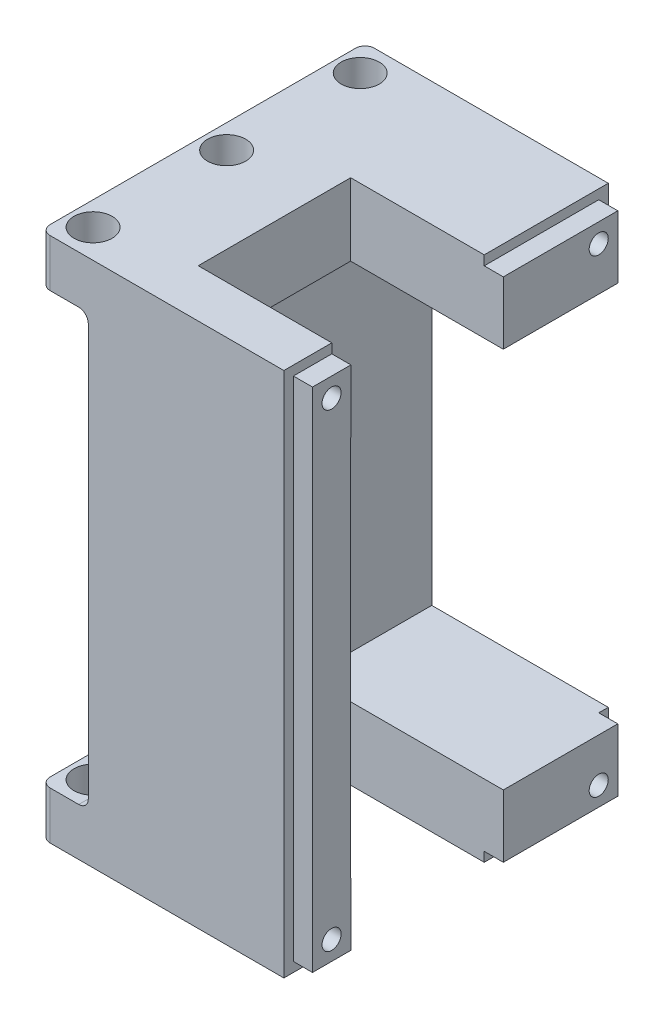
SolidWorks part; units mm, degrees
ref_plane "前视基准面" through (0, 0, 0) normal (0, 0, 1) x (1, 0, 0)
ref_plane "上视基准面" through (0, 0, 0) normal (0, 1, 0) x (1, 0, 0)
ref_plane "右视基准面" through (0, 0, 0) normal (1, 0, 0) x (0, 0, -1)
other "Configuration Table"
sketch "草图1" plane through (0, 0, 0) normal (0, 0, 1) x (1, 0, 0)
  line L0 (-1000, 0) -> (49000, 0) construction
  line L1 (-10.25, -20) -> (10.25, -20)
  line L2 (-10.25, -20) -> (-10.25, 20)
  line L3 (-10.25, 20) -> (10.25, 20)
  line L4 (10.25, -20) -> (10.25, 20)
  line L5 (-10.25, -20) -> (10.25, 20) construction
  line L6 (-10.25, 20) -> (10.25, -20) construction
  line L7 (-5, 15) -> (5, 15)
  line L8 (-5, 15) -> (-5, 25)
  line L9 (-5, 25) -> (5, 25)
  line L10 (5, 15) -> (5, 25)
  line L11 (-5, 15) -> (5, 25) construction
  line L12 (-5, 25) -> (5, 15) construction
  line L14 (-10.25, -35.1417) -> (10.25, -35.1417)
  line L15 (-10.25, -35.1417) -> (-10.25, 35.1417)
  line L16 (-10.25, 35.1417) -> (10.25, 35.1417)
  line L17 (10.25, -35.1417) -> (10.25, 35.1417)
  line L18 (-10.25, -35.1417) -> (10.25, 35.1417) construction
  line L19 (-10.25, 35.1417) -> (10.25, -35.1417) construction
  circle A0 centre (-5, 25) radius 2
  circle A1 centre (5, 25) radius 2
  circle A2 centre (5, -25) radius 2
  circle A3 centre (-5, -25) radius 2
  point P0 (0, 0)
  point P6 (0, 20)
  point P19 (0, 0)
  dimension "D5" = 4
  dimension "D6" = 4
  dimension "D1" = 20.5
  dimension "D2" = 40
  dimension "D3" = 10
  dimension "D4" = 10
extrude "凸台-拉伸1" add sketch "草图1" along normal blind 29 contours A1 L10 L3 L17 L16 L15 L8 A0 L9 | L14 L17 L1 L15 A2 A3 | A1 L9 A0 L8 L3 L10
sketch "草图2" plane through (0, 0, 29) normal (0, 0, 1) x (1, 0, 0)
  line L1 (-10.25, 35.1417) -> (10.25, 35.1417)
  line L2 (-10.25, 35.1417) -> (-10.25, -35.1417)
  line L3 (-10.25, -35.1417) -> (10.25, -35.1417)
  line L4 (10.25, 35.1417) -> (10.25, -35.1417)
extrude "凸台-拉伸2" add sketch "草图2" along normal blind 3
sketch "草图3" plane through (0, 0, 0) normal (0, 0, -1) x (-1, 0, 0)
  line L0 (-10.25, -35.1417) -> (-10.25, -20) construction
  line L1 (-10.25, -27.5709) -> (10.25, -27.5709)
  line L2 (-10.25, -27.5709) -> (-10.25, 27.5709)
  line L3 (-10.25, 27.5709) -> (10.25, 27.5709)
  line L4 (10.25, -27.5709) -> (10.25, 27.5709)
  line L5 (10.25, 20) -> (10.25, 35.1417) construction
  line L7 (-10.25, -35.1417) -> (10.25, -35.1417)
  line L8 (-10.25, -35.1417) -> (-10.25, 35.1417)
  line L9 (-10.25, 35.1417) -> (10.25, 35.1417)
  line L10 (10.25, -35.1417) -> (10.25, 35.1417)
  line M2 (-10.25, -35.1417) -> (10.25, -35.1417)
  line M3 (10.25, -35.1417) -> (10.25, -20)
  line M5 (-10.25, -20) -> (-10.25, -35.1417)
extrude "切除-拉伸1" cut sketch "草图3" against normal through all contours L1 M5 M2 M3 | L3 L10 L9 L8
sketch "草图5" plane through (0, -27.5709, 0) normal (0, -1, 0) x (1, 0, 0)
  line L0 (0, 0) -> (0, 2.5)
  circle A0 centre (0, 2.5) radius 2.5
  dimension "D2" = 5
  dimension "D1" = 2.5
extrude "凸台-拉伸3" add sketch "草图5" along normal blind 10
sketch "草图8" plane through (0, 27.5709, 0) normal (0, 1, 0) x (1, 0, 0)
  line L0 (0, 0) -> (0, -2.5)
  line L1 (0, -2.5) -> (0, -16.5)
  line L2 (0, -16.5) -> (0, -26.5)
  circle A0 centre (0, -16.5) radius 1.6
  circle A1 centre (0, -26.5) radius 1.6
  dimension "D4" = 3.2
  dimension "D5" = 3.2
  dimension "D1" = 2.5
  dimension "D2" = 14
  dimension "D3" = 10
extrude "切除-拉伸2" cut sketch "草图8" against normal up to next
sketch "草图9" plane through (0, -27.5709, 0) normal (0, -1, 0) x (1, 0, 0)
  line L1 (-10.25, 32) -> (10.25, 32)
  line L2 (-10.25, 32) -> (-10.25, 0)
  line L3 (-10.25, 0) -> (10.25, 0)
  line L4 (10.25, 32) -> (10.25, 0)
extrude "切除-拉伸3" cut sketch "草图9" along normal through all
sketch "草图12" plane through (0, 0, 0) normal (0, 0, -1) x (-1, 0, 0)
  line L1 (-10.25, 27.5709) -> (10.25, 27.5709)
  line L2 (-10.25, 27.5709) -> (-10.25, 20)
  line L3 (-10.25, 20) -> (10.25, 20)
  line L4 (10.25, 27.5709) -> (10.25, 20)
  circle A0 centre (-5, 25) radius 2
  circle A1 centre (5, 25) radius 2
extrude "凸台-拉伸5" add sketch "草图12" against normal blind 30
sketch "草图13" plane through (0, 27.5709, 0) normal (0, 1, 0) x (1, 0, 0)
  line L0 (0, 0) -> (0, -32)
  line L1 (10.25, -32) -> (-10.25, -32) construction
  line L2 (0, 0) -> (0, -10)
  line L3 (0, 0) -> (0, -2.5275)
  line L4 (0, 0) -> (0, -5)
  circle A2 centre (0, -5) radius 2.5
  circle A3 centre (0, -5) radius 4
  dimension "D3" = 5
  dimension "D4" = 5
  dimension "D5" = 8
  dimension "D1" = 32
  dimension "D2" = 10
extrude "凸台-拉伸6" add sketch "草图13" along normal blind 10 contours L4 A3 L2 A2 | L2 A3 L4 A2
sketch "草图15" plane through (0, 0, 0) normal (1, 0, 0) x (0, 0, -1)
  line L0 (-1, 27.5709) -> (0, 27.5709)
  line L1 (-1, 27.5709) -> (-1, 28.676)
  line L2 (-1, 27.5709) -> (-1, 37.5709) construction
  line L3 (-5, -962.4291) -> (-5, 49037.5709) construction
  line L4 (-2.5, 37.5709) -> (-7.5, 37.5709) construction
  arc A0 (-1, 28.676) -> (0, 27.5709) centre (0.1107, 28.676) ccw
  point P13 (-5, 37.5709)
revolve "旋转1" add sketch "草图15" angle 360 about L3
ref_plane "基准面1" through (0, 0, 5) normal (0, 0, 1) x (1, 0, 0)
sketch "草图16" plane through (0, 0, 5) normal (0, 0, 1) x (1, 0, 0)
  line L0 (0, 37.5709) -> (0, 33.5709)
  line L1 (2.5, 37.5709) -> (-2.5, 37.5709) construction
  circle A0 centre (0, 33.5709) radius 1.5
  dimension "D2" = 3
  dimension "D1" = 4
extrude "切除-拉伸5" cut sketch "草图16" against normal through all
sketch "草图17" plane through (0, 0, 0) normal (1, 0, 0) x (0, 0, -1)
  line L0 (-5, 37.5709) -> (-5, 33.5709)
  line L1 (-2.5, 37.5709) -> (-7.5, 37.5709) construction
  line L2 (-5, 11.275) -> (-5, -11.275) construction
  circle A0 centre (-5, 33.5709) radius 1.5
  dimension "D2" = 3
  dimension "D1" = 4
extrude "切除-拉伸6" cut sketch "草图17" against normal through all
sketch "草图19" plane through (0, -27.5709, 0) normal (0, -1, 0) x (1, 0, 0)
  line L0 (0, 0) -> (0, 5)
  line L1 (10.25, 0) -> (-10.25, 0) construction
  circle A0 centre (0, 5) radius 2.5
  circle A1 centre (0, 5) radius 4
  dimension "D2" = 5
  dimension "D3" = 8
  dimension "D1" = 5
extrude "凸台-拉伸7" add sketch "草图19" along normal blind 10
sketch "草图20" plane through (0, 0, 0) normal (1, 0, 0) x (0, 0, -1)
  line L0 (-1, -27.5709) -> (0, -27.5709)
  line L1 (-1, -27.5709) -> (-1, -28.5709)
  line L2 (-1, -37.5709) -> (-1, -27.5709) construction
  line L3 (-5, -1027.5709) -> (-5, 48972.4291) construction
  line L4 (-9, -27.5709) -> (-1, -27.5709) construction
  arc A0 (-1, -28.5709) -> (0, -27.5709) centre (0, -28.5709) cw
  point P13 (-5, -27.5709)
  dimension "D1" = 1
revolve "旋转2" add sketch "草图20" angle 360 about L3
sketch "草图21" plane through (0, 0, 5) normal (0, 0, 1) x (1, 0, 0)
  line L0 (0, -37.5709) -> (0, -33.5709)
  line L1 (-4, -37.5709) -> (4, -37.5709) construction
  circle A0 centre (0, -33.5709) radius 1.5
  dimension "D2" = 3
  dimension "D1" = 4
extrude "切除-拉伸7" cut sketch "草图21" against normal through all
sketch "草图22" plane through (0, 0, 0) normal (1, 0, 0) x (0, 0, -1)
  line L0 (-5, -37.5709) -> (-5, -33.5709)
  line L1 (-9, -37.5709) -> (-1, -37.5709) construction
  line L2 (-5, 11.275) -> (-5, -11.275) construction
  circle A0 centre (-5, -33.5709) radius 1.5
  dimension "D2" = 3
  dimension "D1" = 4
extrude "切除-拉伸8" cut sketch "草图22" against normal through all
sketch "草图23" plane through (0, 0, 32) normal (0, 0, 1) x (1, 0, 0)
  line L1 (-10.25, 27.5709) -> (10.25, 27.5709)
  line L2 (-10.25, 27.5709) -> (-10.25, -27.5709)
  line L3 (-10.25, -27.5709) -> (10.25, -27.5709)
  line L4 (10.25, 27.5709) -> (10.25, -27.5709)
extrude "凸台-拉伸8" add sketch "草图23" along normal blind 2
sketch "草图24" plane through (-10.25, 0, 0) normal (-1, 0, 0) x (0, 0, 1)
  line L0 (34, -27.5709) -> (0, -27.5709) construction
  line L1 (34, 27.5709) -> (24, 27.5709)
  line L2 (34, 27.5709) -> (34, -27.5709)
  line L3 (34, -27.5709) -> (24, -27.5709)
  line L4 (24, 27.5709) -> (24, -27.5709)
  dimension "D1" = 10
extrude "凸台-拉伸9" add sketch "草图24" along normal blind 2
sketch "草图25" plane through (10.25, 0, 0) normal (1, 0, 0) x (0, 0, -1)
  line L0 (-34, 27.5709) -> (-21, 27.5709)
  line L1 (-34, 27.5709) -> (0, 27.5709) construction
  line L2 (-21, 27.5709) -> (-17, 27.5709)
  line L3 (-17, 27.5709) -> (-17, -27.5709)
  line L6 (-17, -27.5709) -> (-25, -27.5709)
  line L7 (-34, -27.5709) -> (0, -27.5709) construction
  line L8 (-25, -27.5709) -> (-25, 27.5709)
  line M5 (-29, 20) -> (0, 20)
  line M7 (0, 27.5709) -> (-34, 27.5709)
  line M9 (-34, -27.5709) -> (0, -27.5709)
  line M11 (0, -20) -> (-29, -20)
  dimension "D1" = 13
  dimension "D2" = 4
  dimension "D3" = 8
extrude "切除-拉伸9" cut sketch "草图25" against normal blind 16 contours L8 L3 M9 M11 | L8 L3 M5 M7
sketch "草图26" plane through (0, 0, 29) normal (0, 0, -1) x (-1, 0, 0)
  circle A0 centre (-5, 25) radius 2
  circle A1 centre (5, 25) radius 2
  circle A2 centre (-5, -25) radius 2
  circle A3 centre (5, -25) radius 2
extrude "凸台-拉伸10" add sketch "草图26" along normal blind 20
sketch "草图27" plane through (0, -27.5709, 0) normal (0, -1, 0) x (1, 0, 0)
  line L1 (-5.75, 25) -> (10.25, 25)
  line L2 (-5.75, 25) -> (-5.75, 17)
  line L3 (-5.75, 17) -> (10.25, 17)
  line L4 (10.25, 25) -> (10.25, 17)
extrude "切除-拉伸10" cut sketch "草图27" against normal through all
sketch "草图29" plane through (10.25, 0, 0) normal (1, 0, 0) x (0, 0, -1)
  line L0 (-33, 26.5709) -> (-33, -26.5709)
  line L1 (-34, 27.5709) -> (0, 27.5709)
  line L2 (-34, 27.5709) -> (-34, -27.5709)
  line L3 (-34, -27.5709) -> (0, -27.5709)
  line L4 (0, 27.5709) -> (0, -27.5709)
  line L5 (-33, -26.5709) -> (-1, -26.5709)
  line L6 (-1, 26.5709) -> (-1, -26.5709)
  line L7 (-33, 26.5709) -> (-1, 26.5709)
  dimension "D1" = 1
extrude "切除-拉伸11" cut sketch "草图29" against normal blind 2
sketch "草图30" plane through (10.25, 0, 0) normal (1, 0, 0) x (0, 0, -1)
  line L1 (-34, 27.5709) -> (0, 27.5709)
  line L2 (-34, 27.5709) -> (-34, -27.5709)
  line L3 (-34, -27.5709) -> (0, -27.5709)
  line L4 (0, 27.5709) -> (0, -27.5709)
  dimension "D1" = 34
  dimension "D2" = 55.1417
sketch "草图32" plane through (10.25, 0, 0) normal (1, 0, 0) x (0, 0, -1)
  line L0 (-17, -26.5709) -> (-1, -26.5709) construction
  line L1 (-33, 26.5709) -> (-13, 26.5709)
  line L2 (-33, 26.5709) -> (-33, -26.5709)
  line L3 (-33, -26.5709) -> (-13, -26.5709)
  line L4 (-13, 26.5709) -> (-13, -26.5709)
  line L6 (-13, 26.5709) -> (-28.9769, 26.5709)
  line L7 (-13, 26.5709) -> (-13, -26.5709)
  line L8 (-13, -26.5709) -> (-28.9769, -26.5709)
  line L9 (-28.9769, 26.5709) -> (-28.9769, -26.5709)
  line L10 (-13, -26.5709) -> (-28.9769, -26.5709)
  line L11 (-13, -26.5709) -> (-13, 27.5939)
  line L12 (-13, 27.5939) -> (-28.9769, 27.5939)
  line L13 (-28.9769, -26.5709) -> (-28.9769, 27.5939)
  line L14 (-28.9769, 27.5939) -> (-13, 27.5939)
  line L15 (-28.9769, 27.5939) -> (-28.9769, -27.5919)
  line L16 (-28.9769, -27.5919) -> (-13, -27.5919)
  line L17 (-13, 27.5939) -> (-13, -27.5919)
  line M2 (-25, 26.5709) -> (-33, 26.5709)
  line M5 (-25, -26.5709) -> (-25, -20)
  line M6 (-25, -20) -> (-29, -20)
  line M8 (-29, 20) -> (-25, 20)
  line M9 (-25, 20) -> (-25, 26.5709)
  dimension "D1" = 20
extrude "切除-拉伸13" cut sketch "草图32" against normal blind 16 contours L9 L3 L4 L1 M8 M6 M5 M9 | L9 M2 M8 M9 | L9 L3 M6 M5 | L17 L3 L15 L16 | L13 L1 L11 L12 M2
sketch "草图33" plane through (10.25, 0, 0) normal (1, 0, 0) x (0, 0, -1)
  line L1 (-33, 26.5709) -> (-31, 26.5709)
  line L2 (-33, 26.5709) -> (-33, 24.5709)
  line L3 (-33, 24.5709) -> (-31, 24.5709)
  line L4 (-31, 26.5709) -> (-31, 24.5709)
  line L5 (-33, -26.5709) -> (-31, -26.5709)
  line L6 (-33, -26.5709) -> (-33, -24.5709)
  line L7 (-33, -24.5709) -> (-31, -24.5709)
  line L8 (-31, -26.5709) -> (-31, -24.5709)
  circle A0 centre (-31, 24.5709) radius 1
  circle A1 centre (-31, -24.5709) radius 1
  dimension "D3" = 2
  dimension "D6" = 2
  dimension "D1" = 2
  dimension "D2" = 2
  dimension "D4" = 2
  dimension "D5" = 2
extrude "切除-拉伸14" cut sketch "草图33" against normal blind 16 contours A1 | A0
sketch "草图35" plane through (10.25, 0, 0) normal (1, 0, 0) x (0, 0, -1)
  line L1 (-1, 26.5709) -> (-3, 26.5709)
  line L2 (-1, 26.5709) -> (-1, 24.5709)
  line L3 (-1, 24.5709) -> (-3, 24.5709)
  line L4 (-3, 26.5709) -> (-3, 24.5709)
  line L5 (-1, -26.5709) -> (-3, -26.5709)
  line L6 (-1, -26.5709) -> (-1, -24.5709)
  line L7 (-1, -24.5709) -> (-3, -24.5709)
  line L8 (-3, -26.5709) -> (-3, -24.5709)
  circle A0 centre (-3, 24.5709) radius 1
  circle A1 centre (-3, -24.5709) radius 1
  dimension "D3" = 2
  dimension "D6" = 2
  dimension "D1" = 2
  dimension "D2" = 2
  dimension "D4" = 2
  dimension "D5" = 2
extrude "切除-拉伸15" cut sketch "草图35" against normal blind 5 contours A1 | A0
sketch "草图36" plane through (0, -37.5709, 0) normal (0, -1, 0) x (1, 0, 0)
  circle A1 centre (0, 5) radius 2.65
  dimension "D1" = 5.3
extrude "切除-拉伸16" cut sketch "草图36" against normal blind 10
sketch "草图37" plane through (0, 37.5709, 0) normal (0, 1, 0) x (1, 0, 0)
  circle A0 centre (0, -5) radius 2.65
  dimension "D1" = 5.3
extrude "切除-拉伸17" cut sketch "草图37" against normal blind 10
sketch "草图38" plane through (0, -27.5709, 0) normal (0, -1, 0) x (1, 0, 0)
  line L1 (-28.75, -34) -> (8.25, -34)
  line L2 (-28.75, -34) -> (-28.75, 34)
  line L3 (-28.75, 34) -> (8.25, 34)
  line L4 (8.25, -34) -> (8.25, 34)
  line L5 (-28.75, -34) -> (8.25, 34) construction
  line L6 (-28.75, 34) -> (8.25, -34) construction
  point P0 (-10.25, 0)
extrude "切除-拉伸18" cut sketch "草图38" along normal blind 10
sketch "草图39" plane through (-10.25, 0, 0) normal (-1, 0, 0) x (0, 0, 1)
  line L1 (0, 27.5709) -> (24, 27.5709)
  line L2 (0, 27.5709) -> (0, -27.5709)
  line L3 (0, -27.5709) -> (24, -27.5709)
  line L4 (24, 27.5709) -> (24, -27.5709)
extrude "凸台-拉伸11" add sketch "草图39" along normal blind 2
sketch "草图40" plane through (0, 27.5709, 0) normal (0, 1, 0) x (1, 0, 0)
  line L1 (-12.25, 0) -> (8.25, 0)
  line L2 (-12.25, 0) -> (-12.25, -34)
  line L3 (-12.25, -34) -> (8.25, -34)
  line L4 (8.25, 0) -> (8.25, -34)
extrude "切除-拉伸19" cut sketch "草图40" along normal through all
sketch "草图41" plane through (0, 27.5709, 0) normal (0, 1, 0) x (1, 0, 0)
  line L1 (-12.25, 0) -> (-17.25, 0)
  line L2 (-12.25, 0) -> (-12.25, -34)
  line L3 (-12.25, -34) -> (-17.25, -34)
  line L4 (-17.25, 0) -> (-17.25, -34)
  dimension "D1" = 5
  dimension "D2" = 34
extrude "凸台-拉伸12" add sketch "草图41" against normal blind 5
mirror "镜向1" about plane through (0, 0, 0) normal (0, 1, 0) of "凸台-拉伸12"
sketch "草图42" plane through (0, -27.5709, 0) normal (0, -1, 0) x (1, 0, 0)
  line L0 (-17.25, 34) -> (-14.75, 34)
  line L1 (-17.25, 34) -> (8.25, 34) construction
  line L2 (-14.75, 34) -> (-14.75, 31)
  line L3 (-1017.25, 17) -> (48982.75, 17) construction
  line L4 (-19.75, -3) -> (-14.75, -3)
  line L5 (-19.75, -3) -> (-19.75, 3)
  line L6 (-19.75, 3) -> (-14.75, 3)
  line L7 (-14.75, -3) -> (-14.75, 3)
  line L8 (-19.75, -3) -> (-14.75, 3) construction
  line L9 (-19.75, 3) -> (-14.75, -3) construction
  line L10 (-17.25, 0) -> (-17.25, 34) construction
  line L11 (-17.25, 17) -> (-14.75, 17)
  circle A0 centre (-14.75, 31) radius 2
  circle A1 centre (-14.75, 3) radius 2
  circle A2 centre (-14.75, 17) radius 2
  point P7 (-17.25, 0)
  point P19 (-17.25, 17)
  dimension "D3" = 4
  dimension "D6" = 4
  dimension "D8" = 4
  dimension "D1" = 2.5
  dimension "D2" = 3
  dimension "D4" = 6
  dimension "D5" = 5
  dimension "D7" = 2.5
extrude "切除-拉伸20" cut sketch "草图42" against normal through all
fillet "圆角1" radius 1 1 edges at (-17.25, 25.0709, 34)
fillet "圆角2" radius 1 1 edges at (-17.25, -25.0709, 34)
fillet "圆角3" radius 1 1 edges at (-17.25, -25.0709, 0)
fillet "圆角4" radius 1 1 edges at (-17.25, 25.0709, 0)
fillet "圆角5" radius 1 1 edges at (-12.25, -22.5709, 17)
fillet "圆角6" radius 1 1 edges at (-12.25, 22.5709, 17)
